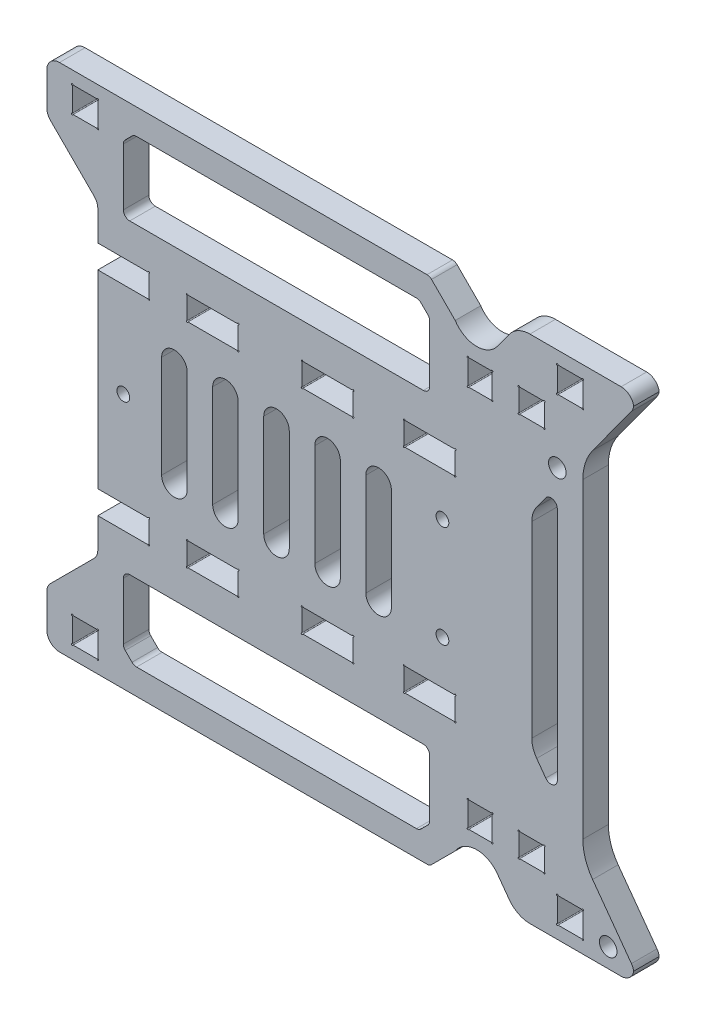
SolidWorks part; units mm, degrees
ref_plane "Front Plane" through (0, 0, 0) normal (0, 0, 1) x (1, 0, 0)
ref_plane "Top Plane" through (0, 0, 0) normal (0, 1, 0) x (1, 0, 0)
ref_plane "Right Plane" through (0, 0, 0) normal (1, 0, 0) x (0, 0, -1)
sketch "Sketch1" plane through (0, 0, 0) normal (0, 0, 1) x (1, 0, 0)
  line L0 (83.672, 0) -> (-43.8164, 0) construction
  line L1 (10.525, 38.1) -> (10.525, -38.1) construction
  line L2 (-27.575, 38.1) -> (48.625, 38.1)
  line L3 (99.425, -63.5) -> (99.425, -60.325)
  line L4 (99.425, -60.325) -> (74.025, -25.4)
  line L5 (-27.575, -63.5) -> (48.625, -63.5)
  line L6 (-27.575, 38.1) -> (-27.575, 54.5197)
  line L7 (48.625, 38.1) -> (48.625, 54.5197)
  line L8 (-24.9447, 57.15) -> (45.9947, 57.15)
  line L9 (-27.575, 63.5) -> (48.625, 63.5)
  line L10 (-33.925, 57.15) -> (-33.925, -57.15)
  line L11 (-27.575, 63.5) -> (-33.925, 57.15)
  line L12 (-24.9447, 57.15) -> (-27.575, 54.5197)
  line L13 (99.425, 63.5) -> (99.425, 60.325)
  line L14 (-23.0849, 59.0099) -> (-29.4349, 52.6599) construction
  line L15 (99.425, 60.325) -> (74.025, 25.4)
  line L16 (74.025, 25.4) -> (74.025, -25.4)
  line L17 (48.625, -38.1) -> (48.625, -54.5197)
  line L18 (-27.575, -38.1) -> (48.625, -38.1)
  line L19 (-24.9447, -57.15) -> (45.9947, -57.15)
  line L20 (-24.9447, -57.15) -> (-27.575, -54.5197)
  line L21 (-27.575, -38.1) -> (-27.575, -54.5197)
  line L22 (-27.575, -63.5) -> (-33.925, -57.15)
  line L23 (48.625, -63.5) -> (54.975, -57.15)
  line L24 (48.625, 63.5) -> (54.975, 57.15)
  line L25 (70.3271, -63.5) -> (99.425, -63.5)
  line L26 (45.9947, 57.15) -> (48.625, 54.5197)
  line L27 (45.9947, -57.15) -> (48.625, -54.5197)
  line L28 (70.3271, 63.5) -> (65.7089, 57.15)
  line L29 (70.3271, 63.5) -> (99.425, 63.5)
  line L30 (78.8831, 75.2646) -> (53.4831, 40.3396) construction
  line L31 (54.975, -42.3909) -> (54.975, -57.15)
  line L32 (70.3271, -63.5) -> (65.7089, -57.15)
  line L34 (48.625, -63.5) -> (54.975, -57.15)
  line L35 (65.7089, 57.15) -> (54.975, 42.3909)
  line L36 (54.975, 42.3909) -> (54.975, 57.15)
  line L37 (65.7089, -57.15) -> (54.975, -42.3909)
  point P7 (-27.575, 0)
  point P21 (74.025, 0)
  point P22 (-33.925, 0)
  dimension "D1" = 25.4
  dimension "D2" = 76.2
  dimension "D3" = 127
  dimension "D4" = 6.35
  dimension "D7" = 3.175
  dimension "D8" = 25.4
  dimension "D9" = 25.4
  dimension "D6" = 6.35
extrude "Boss-Extrude1" add sketch "Sketch1" along normal blind 6.35 contours L23 L32 L25 L3 L4 L16 L15 L13 L29 L28 L24 L9 L11 L10 L22 L5 L8 L26 L7 L2 L6 L12 L27 L19 L20 L21 L18 L17 region at (27.1557, 0, 0)
fillet "Fillet1" radius 6.35 4 edges at (70.3271, 63.5, 3.175) (70.3271, -63.5, 3.175) (54.975, -42.3909, 3.175) (54.975, 42.3909, 3.175)
fillet "Fillet3" radius 3.175 4 edges at (99.425, 63.5, 3.175) (99.425, 60.325, 3.175) (99.425, -60.325, 3.175) (99.425, -63.5, 3.175)
fillet "Fillet4" radius 6.35 2 edges at (74.025, -25.4, 3.175) (74.025, 25.4, 3.175)
fillet "Fillet7" radius 1.5875 4 edges at (-27.575, -38.1, 3.175) (48.625, -38.1, 3.175) (48.625, 38.1, 3.175) (-27.575, 38.1, 3.175)
fillet "Fillet8" radius 1.5875 2 edges at (48.625, -63.5, 3.175) (48.625, 63.5, 3.175)
fillet "Fillet9" radius 1.5875 8 edges at (-27.575, 54.5197, 3.175) (-24.9447, 57.15, 3.175) (-27.575, -54.5197, 3.175) (-24.9447, -57.15, 3.175) (45.9947, -57.15, 3.175) (48.625, -54.5197, 3.175) (48.625, 54.5197, 3.175) (45.9947, 57.15, 3.175)
sketch "Sketch2" plane through (0, 0, 6.35) normal (0, 0, 1) x (1, 0, 0)
  line L0 (-33.925, 0) -> (74.025, 0) construction
  line L1 (-33.925, 57.15) -> (-33.925, -57.15) construction
  line L2 (74.025, 23.3351) -> (74.025, -23.3351) construction
  line L3 (48.625, 39.6875) -> (48.625, 53.8622) construction
  line L4 (58.3484, 50.8) -> (63.9714, 50.8)
  line L5 (58.15, 50.6016) -> (58.15, 44.6484)
  line L6 (58.3484, 44.45) -> (63.9714, 44.45)
  line L7 (64.1698, 50.6016) -> (64.1698, 44.6484)
  line L8 (64.1698, -50.6016) -> (64.1698, -44.6484)
  line L9 (58.3484, -50.8) -> (63.9714, -50.8)
  line L10 (58.15, -50.6016) -> (58.15, -44.6484)
  line L11 (58.3484, -44.45) -> (63.9714, -44.45)
  arc A0 (58.3484, 50.8) -> (58.15, 50.6016) centre (58.15, 50.8) ccw
  arc A1 (64.1698, 50.6016) -> (63.9714, 50.8) centre (64.1698, 50.8) ccw
  arc A2 (63.9714, 44.45) -> (64.1698, 44.6484) centre (64.1698, 44.45) ccw
  arc A3 (58.15, 44.6484) -> (58.3484, 44.45) centre (58.15, 44.45) ccw
  arc A4 (63.9714, -44.45) -> (64.1698, -44.6484) centre (64.1698, -44.45) cw
  arc A5 (64.1698, -50.6016) -> (63.9714, -50.8) centre (64.1698, -50.8) cw
  arc A6 (58.3484, -50.8) -> (58.15, -50.6016) centre (58.15, -50.8) cw
  arc A7 (58.15, -44.6484) -> (58.3484, -44.45) centre (58.15, -44.45) cw
  point P10 (48.625, 46.7748)
  dimension "D5" = 0.3969
  dimension "D6" = 0.3969
  dimension "D7" = 0.3969
  dimension "D8" = 0.3969
  dimension "D1" = 6.0198
  dimension "D2" = 6.35
  dimension "D3" = 50.8
  dimension "D4" = 9.525
extrude "Cut-Extrude1" cut sketch "Sketch2" against normal through all
sketch "Sketch5" plane through (0, 0, 6.35) normal (0, 0, 1) x (1, 0, 0)
  line L0 (-33.925, 29.3675) -> (74.025, 29.3675) construction
  line L1 (-33.925, 57.15) -> (-33.925, -57.15) construction
  line L2 (74.025, 23.3351) -> (74.025, -23.3351) construction
  line L3 (-25.9875, 38.1) -> (47.0375, 38.1) construction
  line L4 (-33.925, 23.5763) -> (74.025, 23.5763) construction
  line L5 (-33.925, 0) -> (74.025, 0) construction
  line L6 (-11.5016, 29.3675) -> (0.8016, 29.3675)
  line L7 (-11.7, 29.169) -> (-11.7, 23.7747)
  line L8 (-11.5016, 23.5763) -> (0.8016, 23.5763)
  line L9 (1, 29.169) -> (1, 23.7747)
  line L10 (42.4734, 29.3675) -> (54.7766, 29.3675)
  line L11 (42.275, 29.169) -> (42.275, 23.7747)
  line L12 (42.4734, 23.5763) -> (54.7766, 23.5763)
  line L13 (54.975, 29.169) -> (54.975, 23.7747)
  line L14 (29.3766, 29.3675) -> (17.0734, 29.3675)
  line L15 (29.575, 29.169) -> (29.575, 23.7747)
  line L16 (29.3766, 23.5763) -> (17.0734, 23.5763)
  line L17 (16.875, 29.169) -> (16.875, 23.7747)
  line L18 (-21.4234, 29.3675) -> (-33.925, 29.3675)
  line L19 (-21.225, 29.169) -> (-21.225, 23.7747)
  line L20 (-21.4234, 23.5763) -> (-33.925, 23.5763)
  line L21 (-33.925, 29.3675) -> (-33.925, 23.5763)
  line L22 (-33.925, -29.3675) -> (-33.925, -23.5763)
  line L23 (-21.4234, -23.5763) -> (-33.925, -23.5763)
  line L24 (-21.225, -29.169) -> (-21.225, -23.7747)
  line L25 (-21.4234, -29.3675) -> (-33.925, -29.3675)
  line L26 (16.875, -29.169) -> (16.875, -23.7747)
  line L27 (29.3766, -23.5763) -> (17.0734, -23.5763)
  line L28 (29.575, -29.169) -> (29.575, -23.7747)
  line L29 (29.3766, -29.3675) -> (17.0734, -29.3675)
  line L30 (54.975, -29.169) -> (54.975, -23.7747)
  line L31 (42.4734, -23.5763) -> (54.7766, -23.5763)
  line L32 (42.275, -29.169) -> (42.275, -23.7747)
  line L33 (42.4734, -29.3675) -> (54.7766, -29.3675)
  line L34 (1, -29.169) -> (1, -23.7747)
  line L35 (-11.5016, -23.5763) -> (0.8016, -23.5763)
  line L36 (-11.7, -29.169) -> (-11.7, -23.7747)
  line L37 (-11.5016, -29.3675) -> (0.8016, -29.3675)
  line L38 (-33.925, 26.4719) -> (54.975, 26.4719) construction
  arc A0 (-21.225, 29.169) -> (-21.4234, 29.3675) centre (-21.225, 29.3675) ccw
  arc A1 (-11.5016, 29.3675) -> (-11.7, 29.169) centre (-11.7, 29.3675) ccw
  arc A2 (1, 29.169) -> (0.8016, 29.3675) centre (1, 29.3675) ccw
  arc A3 (29.575, 29.169) -> (29.3766, 29.3675) centre (29.575, 29.3675) ccw
  arc A4 (17.0734, 29.3675) -> (16.875, 29.169) centre (16.875, 29.3675) ccw
  arc A5 (54.975, 29.169) -> (54.7766, 29.3675) centre (54.975, 29.3675) ccw
  arc A6 (42.4734, 29.3675) -> (42.275, 29.169) centre (42.275, 29.3675) ccw
  arc A7 (17.0734, 23.5763) -> (16.875, 23.7747) centre (16.875, 23.5763) cw
  arc A8 (29.575, 23.7747) -> (29.3766, 23.5763) centre (29.575, 23.5763) cw
  arc A9 (42.4734, 23.5763) -> (42.275, 23.7747) centre (42.275, 23.5763) cw
  arc A10 (54.975, 23.7747) -> (54.7766, 23.5763) centre (54.975, 23.5763) cw
  arc A11 (1, 23.7747) -> (0.8016, 23.5763) centre (1, 23.5763) cw
  arc A12 (-11.5016, 23.5763) -> (-11.7, 23.7747) centre (-11.7, 23.5763) cw
  arc A13 (-21.225, 23.7747) -> (-21.4234, 23.5763) centre (-21.225, 23.5763) cw
  arc A14 (-21.225, -23.7747) -> (-21.4234, -23.5763) centre (-21.225, -23.5763) ccw
  arc A15 (-11.5016, -23.5763) -> (-11.7, -23.7747) centre (-11.7, -23.5763) ccw
  arc A16 (1, -23.7747) -> (0.8016, -23.5763) centre (1, -23.5763) ccw
  arc A17 (54.975, -23.7747) -> (54.7766, -23.5763) centre (54.975, -23.5763) ccw
  arc A18 (42.4734, -23.5763) -> (42.275, -23.7747) centre (42.275, -23.5763) ccw
  arc A19 (29.575, -23.7747) -> (29.3766, -23.5763) centre (29.575, -23.5763) ccw
  arc A20 (17.0734, -23.5763) -> (16.875, -23.7747) centre (16.875, -23.5763) ccw
  arc A21 (42.4734, -29.3675) -> (42.275, -29.169) centre (42.275, -29.3675) cw
  arc A22 (54.975, -29.169) -> (54.7766, -29.3675) centre (54.975, -29.3675) cw
  arc A23 (17.0734, -29.3675) -> (16.875, -29.169) centre (16.875, -29.3675) cw
  arc A24 (29.575, -29.169) -> (29.3766, -29.3675) centre (29.575, -29.3675) cw
  arc A25 (1, -29.169) -> (0.8016, -29.3675) centre (1, -29.3675) cw
  arc A26 (-11.5016, -29.3675) -> (-11.7, -29.169) centre (-11.7, -29.3675) cw
  arc A27 (-21.225, -29.169) -> (-21.4234, -29.3675) centre (-21.225, -29.3675) cw
  dimension "D11" = 0.3969
  dimension "D12" = 0.3969
  dimension "D13" = 0.3969
  dimension "D14" = 0.3969
  dimension "D15" = 0.3969
  dimension "D16" = 0.3969
  dimension "D17" = 0.3969
  dimension "D1" = 8.7325
  dimension "D3" = 12.7
  dimension "D4" = 12.7
  dimension "D5" = 41.275
  dimension "D6" = 34.925
  dimension "D7" = 12.7
  dimension "D8" = 12.7
  dimension "D9" = 50.8
  dimension "D10" = 0
  dimension "D2" = 5.7912
extrude "Cut-Extrude4" cut sketch "Sketch5" against normal through all
sketch "Sketch6" plane through (0, 0, 6.35) normal (0, 0, 1) x (1, 0, 0)
  line L0 (80.375, 34.1312) -> (80.375, -34.1312)
  line L1 (98.8177, 59.49) -> (75.2395, 27.07) construction
  line L2 (98.8177, -59.49) -> (75.2395, -27.07) construction
  line L3 (74.025, 23.3351) -> (74.025, -23.3351) construction
  line L4 (86.725, 34.1312) -> (86.725, -34.1312)
  line L5 (86.725, 34.1312) -> (86.725, 42.8625)
  line L6 (86.725, 42.8625) -> (80.375, 34.1312)
  line L7 (86.725, -34.1312) -> (86.725, -42.8625)
  line L8 (86.725, -42.8625) -> (80.375, -34.1312)
  dimension "D1" = 6.35
  dimension "D2" = 6.35
extrude "Boss-Extrude2" add sketch "Sketch6" against normal blind 6.35
fillet "Fillet10" radius 1.5875 2 edges at (80.375, -34.1312, 3.175) (80.375, 34.1312, 3.175)
fillet "Fillet11" radius 12.7 2 edges at (86.725, 42.8625, 3.175) (86.725, -42.8625, 3.175)
hole_wizard "11/64 (0.17188) Diameter Hole1" positions "Sketch8" profile "Sketch7" hole size "11/64" standard "ANSI Inch" end condition through all
sketch "Sketch8" plane through (0, 0, 6.35) normal (0, 0, 1) x (1, 0, 0)
  line L1 (-33.925, -29.3675) -> (-33.925, -57.15) construction
  line L2 (73.5606, 63.5) -> (96.25, 63.5) construction
  point P0 (80.375, 38.1)
  dimension "D1" = 25.4
  dimension "D2" = 114.3
sketch "Sketch7" plane through (80.375, 38.1, 6.35) normal (1, 0, 0) x (0, -1, 0)
  line L0 (0, 0) -> (0, 6.35)
  line L1 (0, 6.35) -> (2.1829, 6.35)
  line L2 (2.1829, 6.35) -> (2.1829, 0)
  line L5 (2.1829, 0) -> (0, 0)
  line L11 (0, -6.35) -> (0, 107.95) construction
  dimension "Thru Hole Dia." = 4.3658
  dimension "Thru Hole Depth" = 6.35
sketch "Sketch10" plane through (0, 0, 6.35) normal (0, 0, 1) x (1, 0, 0)
  line L0 (51.8, 63.5) -> (51.8, -63.5) construction
  line L1 (-27.575, 63.5) -> (47.9674, 63.5) construction
  line L2 (-27.575, -63.5) -> (47.9674, -63.5) construction
  line L3 (23.225, 29.3675) -> (23.225, -29.3675) construction
  line L4 (29.3766, 29.3675) -> (17.0734, 29.3675) construction
  line L5 (17.0734, -29.3675) -> (29.3766, -29.3675) construction
  line L6 (-27.575, 63.5) -> (-27.575, -63.5) construction
  line L7 (-33.925, 0) -> (74.025, 0) construction
  line L8 (-33.925, 23.5763) -> (-33.925, -23.5763) construction
  line L9 (74.025, 23.3351) -> (74.025, -23.3351) construction
  circle A0 centre (51.8, 12.7) radius 1.5875
  circle A1 centre (51.8, -12.7) radius 1.5875
  circle A2 centre (-27.575, 0) radius 1.5875
  dimension "D3" = 3.175
  dimension "D5" = 79.375
  dimension "D1" = 28.575
  dimension "D2" = 79.375
  dimension "D4" = 12.7
extrude "Cut-Extrude6" cut sketch "Sketch10" against normal through all
sketch "Sketch11" plane through (0, 0, 6.35) normal (0, 0, 1) x (1, 0, 0)
  line L0 (-62.0481, -60.325) -> (124.8486, -60.325) construction
  line L1 (-27.575, -63.5) -> (47.9674, -63.5) construction
  line L2 (-27.575, -63.5) -> (-33.925, -57.15)
  line L3 (-33.925, -57.15) -> (-33.925, -50.8)
  line L4 (-33.925, -50.8) -> (-33.925, -38.1)
  line L5 (-46.625, -50.8) -> (-46.625, -63.5)
  line L6 (-46.625, -63.5) -> (-27.575, -63.5)
  line L7 (-46.625, -50.8) -> (-33.925, -38.1)
  line L8 (-33.925, -29.3675) -> (-33.925, -57.15) construction
  line L9 (-46.625, 63.5) -> (-27.575, 63.5)
  line L10 (-33.925, 0) -> (74.025, 0) construction
  line L11 (-46.625, 50.8) -> (-46.625, 63.5)
  line L12 (-33.925, 23.5763) -> (-33.925, -23.5763) construction
  line L13 (74.025, 23.3351) -> (74.025, -23.3351) construction
  line L14 (-46.625, 50.8) -> (-33.925, 38.1)
  line L15 (-33.925, 57.15) -> (-33.925, 50.8)
  line L16 (-27.575, 63.5) -> (-33.925, 57.15)
  line L17 (-33.925, 50.8) -> (-33.925, 38.1)
  point P2 (10.1962, -63.5)
  dimension "D1" = 3.175
  dimension "D2" = 12.7
  dimension "D3" = 12.7
extrude "Boss-Extrude4" add sketch "Sketch11" against normal blind 6.35
sketch "Sketch12" plane through (0, 0, 6.35) normal (0, 0, 1) x (1, 0, 0)
  line L0 (73.5606, -63.5) -> (96.25, -63.5) construction
  line L1 (86.5266, -60.325) -> (80.5734, -60.325)
  line L2 (86.725, -60.1266) -> (86.725, -54.1734)
  line L3 (86.5266, -53.975) -> (80.5734, -53.975)
  line L4 (80.375, -60.1266) -> (80.375, -54.1734)
  line L5 (-33.925, -29.3675) -> (-33.925, -38.1) construction
  line L6 (-33.925, 0) -> (74.025, 0) construction
  line L7 (86.725, 60.1266) -> (86.725, 54.1734)
  line L8 (86.5266, 60.325) -> (80.5734, 60.325)
  line L9 (80.375, 60.1266) -> (80.375, 54.1734)
  line L10 (86.5266, 53.975) -> (80.5734, 53.975)
  line L11 (83.55, -60.325) -> (-33.7266, -60.325) construction
  line L12 (-34.1234, -60.325) -> (-54.5439, -60.325) construction
  line L13 (-34.1234, -60.325) -> (-40.0766, -60.325)
  line L14 (-33.925, -60.1266) -> (-33.925, -54.1734)
  line L15 (-34.1234, -53.975) -> (-40.0766, -53.975)
  line L16 (-40.275, -60.1266) -> (-40.275, -54.1734)
  line L17 (-34.1234, 60.325) -> (-40.0766, 60.325)
  line L18 (-33.925, 60.1266) -> (-33.925, 54.1734)
  line L19 (-40.275, 60.1266) -> (-40.275, 54.1734)
  line L20 (-34.1234, 53.975) -> (-40.0766, 53.975)
  arc A0 (-40.275, 60.1266) -> (-40.0766, 60.325) centre (-40.275, 60.325) cw
  arc A1 (80.5734, -53.975) -> (80.375, -54.1734) centre (80.375, -53.975) ccw
  arc A2 (86.725, -54.1734) -> (86.5266, -53.975) centre (86.725, -53.975) ccw
  arc A3 (80.375, -60.1266) -> (80.5734, -60.325) centre (80.375, -60.325) ccw
  arc A4 (86.5266, -60.325) -> (86.725, -60.1266) centre (86.725, -60.325) ccw
  arc A5 (86.5266, 60.325) -> (86.725, 60.1266) centre (86.725, 60.325) cw
  arc A6 (80.375, 60.1266) -> (80.5734, 60.325) centre (80.375, 60.325) cw
  arc A7 (80.5734, 53.975) -> (80.375, 54.1734) centre (80.375, 53.975) cw
  arc A8 (86.725, 54.1734) -> (86.5266, 53.975) centre (86.725, 53.975) cw
  arc A9 (-40.0766, -53.975) -> (-40.275, -54.1734) centre (-40.275, -53.975) ccw
  arc A10 (-33.925, -54.1734) -> (-34.1234, -53.975) centre (-33.925, -53.975) ccw
  arc A11 (-34.1234, -60.325) -> (-33.925, -60.1266) centre (-33.925, -60.325) ccw
  arc A12 (-40.275, -60.1266) -> (-40.0766, -60.325) centre (-40.275, -60.325) ccw
  arc A13 (-34.1234, 60.325) -> (-33.925, 60.1266) centre (-33.925, 60.325) cw
  arc A14 (-33.925, 54.1734) -> (-34.1234, 53.975) centre (-33.925, 53.975) cw
  arc A15 (-40.0766, 53.975) -> (-40.275, 54.1734) centre (-40.275, 53.975) cw
  point P4 (84.9053, -63.5)
  dimension "D5" = 0.3969
  dimension "D6" = 0.3969
  dimension "D7" = 0.3969
  dimension "D8" = 0.3969
  dimension "D12" = 0.3969
  dimension "D13" = 0.3969
  dimension "D14" = 0.3969
  dimension "D15" = 0.3969
  dimension "D1" = 6.35
  dimension "D2" = 6.35
  dimension "D3" = 3.175
  dimension "D4" = 114.3
  dimension "D9" = 6.35
  dimension "D10" = 6.35
  dimension "D11" = 120.65
extrude "Cut-Extrude7" cut sketch "Sketch12" against normal blind 6.35
fillet "Fillet12" radius 3.175 6 edges at (-46.625, 63.5, 3.175) (-46.625, 50.8, 3.175) (-33.925, 38.1, 3.175) (-46.625, -63.5, 3.175) (-46.625, -50.8, 3.175) (-33.925, -38.1, 3.175)
hole_wizard "11/64 (0.17188) Diameter Hole2" positions "Sketch14" profile "Sketch13" hole size "11/64" standard "ANSI Inch" end condition through all
sketch "Sketch14" plane through (0, 0, 0) normal (0, 0, -1) x (-1, 0, 0)
  line L0 (-73.5606, -63.5) -> (-96.25, -63.5) construction
  point P0 (-93.0328, -58.7375)
  dimension "D1" = 4.7625
  dimension "D2" = 6.35
sketch "Sketch13" plane through (93.0328, -58.7375, 0) normal (1, 0, 0) x (0, 1, 0)
  line L0 (0, 0) -> (0, 6.35)
  line L1 (0, 6.35) -> (2.1829, 6.35)
  line L2 (2.1829, 6.35) -> (2.1829, 0)
  line L5 (2.1829, 0) -> (0, 0)
  line L11 (0, -6.35) -> (0, 107.95) construction
  dimension "Thru Hole Dia." = 4.3658
  dimension "Thru Hole Depth" = 6.35
sketch "Sketch15" plane through (0, 0, 6.35) normal (0, 0, 1) x (1, 0, 0)
  line L0 (-33.925, 0) -> (86.725, 0) construction
  line L1 (-33.925, 23.5763) -> (-33.925, -23.5763) construction
  line L2 (86.725, -38.7327) -> (86.725, 38.7327) construction
  line L3 (-14.875, -12.7) -> (-14.875, 12.7) construction
  line L4 (-18.05, -12.7) -> (-18.05, 12.7)
  line L5 (-11.7, -12.7) -> (-11.7, 12.7)
  line L6 (-2.175, -12.7) -> (-2.175, 12.7) construction
  line L7 (-5.35, -12.7) -> (-5.35, 12.7)
  line L8 (1, -12.7) -> (1, 12.7)
  line L9 (10.525, -12.7) -> (10.525, 12.7) construction
  line L10 (7.35, -12.7) -> (7.35, 12.7)
  line L11 (13.7, -12.7) -> (13.7, 12.7)
  line L12 (23.225, -12.7) -> (23.225, 12.7) construction
  line L13 (20.05, -12.7) -> (20.05, 12.7)
  line L14 (26.4, -12.7) -> (26.4, 12.7)
  line L15 (35.925, -12.7) -> (35.925, 12.7) construction
  line L16 (32.75, -12.7) -> (32.75, 12.7)
  line L17 (39.1, -12.7) -> (39.1, 12.7)
  arc A0 (-18.05, -12.7) -> (-11.7, -12.7) centre (-14.875, -12.7) ccw
  arc A1 (-11.7, 12.7) -> (-18.05, 12.7) centre (-14.875, 12.7) ccw
  arc A2 (-5.35, -12.7) -> (1, -12.7) centre (-2.175, -12.7) ccw
  arc A3 (1, 12.7) -> (-5.35, 12.7) centre (-2.175, 12.7) ccw
  arc A4 (7.35, -12.7) -> (13.7, -12.7) centre (10.525, -12.7) ccw
  arc A5 (13.7, 12.7) -> (7.35, 12.7) centre (10.525, 12.7) ccw
  arc A6 (20.05, -12.7) -> (26.4, -12.7) centre (23.225, -12.7) ccw
  arc A7 (26.4, 12.7) -> (20.05, 12.7) centre (23.225, 12.7) ccw
  arc A8 (32.75, -12.7) -> (39.1, -12.7) centre (35.925, -12.7) ccw
  arc A9 (39.1, 12.7) -> (32.75, 12.7) centre (35.925, 12.7) ccw
  point P8 (-14.875, 0)
  point P17 (-2.175, 0)
  point P24 (10.525, 0)
  point P31 (23.225, 0)
  point P38 (35.925, 0)
  dimension "D1" = 19.05
  dimension "D2" = 5
extrude "Cut-Extrude8" cut sketch "Sketch15" against normal through all
sketch "Sketch16" plane through (0, 0, 6.35) normal (0, 0, 1) x (1, 0, 0)
  line L0 (73.5606, 63.5) -> (96.25, 63.5) construction
  line L1 (76.9593, 50.8) -> (71.0062, 50.8)
  line L2 (77.1578, 50.6016) -> (77.1578, 45.1564)
  line L3 (76.9593, 44.958) -> (71.0062, 44.958)
  line L4 (70.8078, 50.6016) -> (70.8078, 45.1564)
  line L5 (-33.925, 0) -> (86.725, 0) construction
  line L6 (-33.925, 23.5763) -> (-33.925, -23.5763) construction
  line L7 (86.725, -38.7327) -> (86.725, 38.7327) construction
  line L8 (70.8078, -50.6016) -> (70.8078, -45.1564)
  line L9 (76.9593, -44.958) -> (71.0062, -44.958)
  line L10 (77.1578, -50.6016) -> (77.1578, -45.1564)
  line L11 (76.9593, -50.8) -> (71.0062, -50.8)
  arc A0 (71.0062, 50.8) -> (70.8078, 50.6016) centre (70.8078, 50.8) ccw
  arc A1 (77.1578, 50.6016) -> (76.9593, 50.8) centre (77.1578, 50.8) ccw
  arc A2 (76.9593, 44.958) -> (77.1578, 45.1564) centre (77.1578, 44.958) ccw
  arc A3 (70.8078, 45.1564) -> (71.0062, 44.958) centre (70.8078, 44.958) ccw
  arc A4 (70.8078, -45.1564) -> (71.0062, -44.958) centre (70.8078, -44.958) cw
  arc A5 (76.9593, -44.958) -> (77.1578, -45.1564) centre (77.1578, -44.958) cw
  arc A6 (77.1578, -50.6016) -> (76.9593, -50.8) centre (77.1578, -50.8) cw
  arc A7 (71.0062, -50.8) -> (70.8078, -50.6016) centre (70.8078, -50.8) cw
  dimension "D5" = 0.3969
  dimension "D6" = 0.3969
  dimension "D7" = 0.3969
  dimension "D8" = 0.3969
  dimension "D1" = 6.35
  dimension "D2" = 5.842
  dimension "D3" = 22.225
  dimension "D4" = 12.7
extrude "Cut-Extrude9" cut sketch "Sketch16" against normal through all
